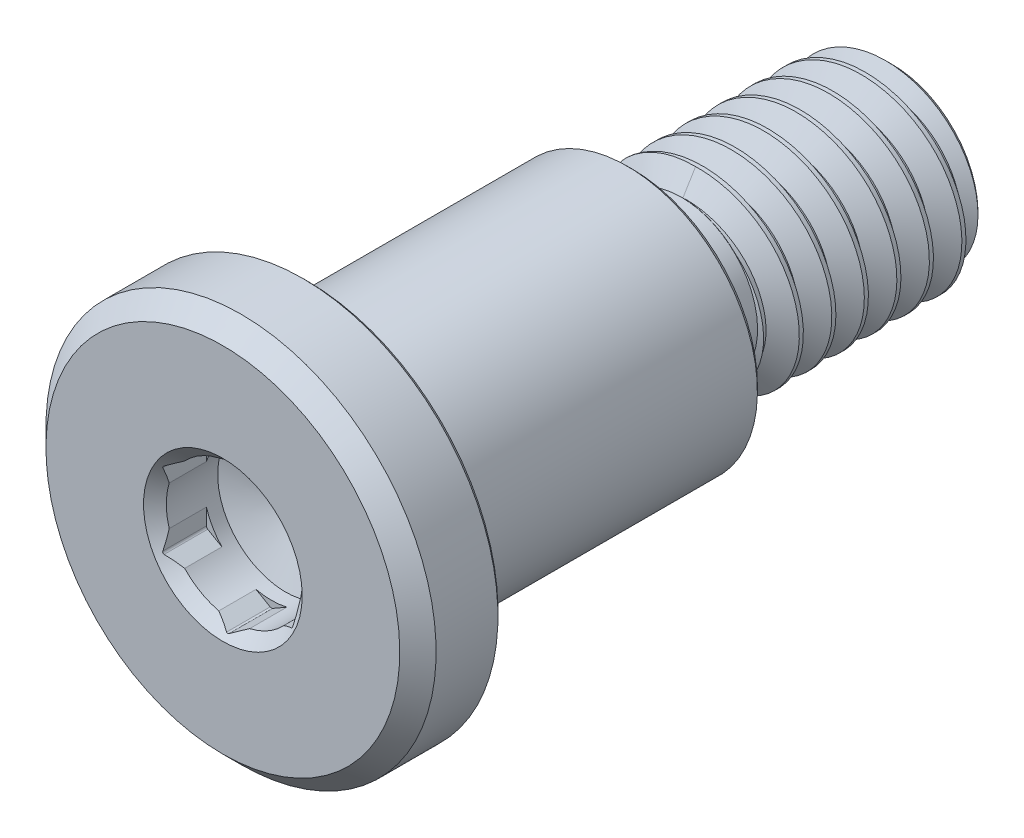
SolidWorks part; units mm, degrees
ref_plane "Front Plane" through (0, 0, 0) normal (0, 0, 1) x (1, 0, 0)
ref_plane "Top Plane" through (0, 0, 0) normal (0, 1, 0) x (1, 0, 0)
ref_plane "Right Plane" through (0, 0, 0) normal (1, 0, 0) x (0, 0, -1)
sketch "Sketch1" plane through (0, 0, 0) normal (1, 0, 0) x (0, 0, -1)
  line L0 (9, 0) -> (0, 0) construction
  line L1 (0, 0) -> (-1.3, 0) construction
  line L2 (-1.3, 3) -> (-1.3, -3) construction
  line L3 (0, 3) -> (0, -3) construction
  line L4 (5, 1.5) -> (9, 1.5) construction
  line L5 (8.9688, 1.5541) -> (9.4688, 1.5541) construction
  line L6 (9.4688, 1.5541) -> (9.2188, 1.1211) construction
  line L7 (9.2188, 1.1211) -> (8.9688, 1.5541) construction
  line L8 (9, 1.5) -> (9.4375, 1.5) construction
  line L9 (9.1875, 1.1752) -> (9.25, 1.1752) construction
  line L10 (9.2188, 1.1211) -> (9.2188, 1.1752) construction
  line L11 (9.2188, 1.5) -> (9.2188, 1.5541) construction
  line L12 (-1.3, 1) -> (-0.335, 1) construction
  line L13 (-0.335, 1) -> (-0.335, -1) construction
  line L14 (-0.335, -1) -> (-1.3, -1) construction
  line L15 (5, 2) -> (5, -2) construction
  line L16 (-1.3, 3) -> (0, 3) construction
  line L17 (5, -1.5) -> (9, -1.5) construction
  point P12 (-0.335, 0)
  point P27 (5, 0)
  point P36 (8.25, -1.5)
  dimension "Screw Size Decimal Equivalent" = 3
  dimension "Thread Length" = 4
  dimension "Shoulder Diameter" = 4
  dimension "Head Height" = 1.3
  dimension "Head Diameter" = 6
  dimension "Drive Size" = 2
  dimension "Thread Pitch" = 0.5
  dimension "Pitch/8" = 0.0625
  dimension "Thread Note" = 0.75
  dimension "Shoulder Length" = 5
  dimension "Approximate Drive Depth" = 0.965
sketch "Sketch2" plane through (0, 0, 0) normal (1, 0, 0) x (0, 0, -1)
  line L0 (-1.3, 3) -> (0, 3)
  line L1 (0, 3) -> (0, 2)
  line L2 (0, 2) -> (5, 2)
  line L3 (5, 2) -> (5, 1.5)
  line L4 (5, 1.5) -> (9, 1.5)
  line L5 (9, 1.5) -> (9, 0)
  line L6 (9, 0) -> (-1.3, 0)
  line L7 (-1.3, 0) -> (-1.3, 3)
revolve "Revolve1" add sketch "Sketch2" angle 360 about L1
chamfer "Chamfer1" distance 0.2795 angle 45 1 edges at (0, 3, 1.3)
chamfer "Chamfer4" distance 0.0699 angle 45 1 edges at (0, 3, 0)
sketch "Sketch3" plane through (0, 0, 0) normal (1, 0, 0) x (0, 0, -1)
  line L0 (0, 2) -> (0.4249, 2)
  line L1 (5, 2) -> (0, 2) construction
  line L2 (0.4249, 2) -> (0.3005, 1.8755)
  line L3 (0, 3) -> (0, -3) construction
  line L4 (0, 1.824) -> (0.176, 1.824) construction
  arc A0 (0.3005, 1.8755) -> (0, 2) centre (0.176, 2) cw
  dimension "D2" = 0.176
  dimension "D1" = 45
revolve "Cut-Revolve1" cut sketch "Sketch3" angle 360 about L0
sketch "Sketch4" plane through (0, 0, 0) normal (1, 0, 0) x (0, 0, -1)
  line L0 (5, 1.5) -> (9, 1.5) construction
  line L1 (5, 1.5) -> (5.939, 1.5)
  line L2 (5, 1.5) -> (5, 1.1727)
  line L3 (5, 1.1727) -> (5.75, 1.1727)
  line L4 (5.939, 1.5) -> (5.75, 1.1727)
  line L5 (5, 2) -> (5, -2) construction
  line L7 (9.1875, 1.1752) -> (9.25, 1.1752) construction
  point P8 (5.7515, 1.1752)
  dimension "D2" = 60
  dimension "D3" = 0.0025
revolve "Cut-Revolve2" cut sketch "Sketch4" angle 360 about L0
chamfer "Chamfer2" distance 0.08 angle 45 1 edges at (0, 2, -5)
fillet "Fillet1" radius 0.064 1 edges at (0, 1.1727, -5)
chamfer "Chamfer3" distance 0.1875 angle 45 1 edges at (0, 1.5, -9)
sketch "Sketch11" plane through (0, 0, 1.3) normal (0, 0, 1) x (1, 0, 0)
  circle A0 centre (0, 0) radius 1.045
  dimension "D1" = 2.09
extrude "Cut-Extrude4" cut sketch "Sketch11" against normal up to vertex (0.965 mm away) up to point (0, 1, 0.335)
sketch "Sketch5" plane through (0, 0, 1.3) normal (0, 0, 1) x (1, 0, 0)
  line L1 (0, 1.1547) -> (-1, 0.5774)
  line L2 (-1, 0.5774) -> (-1, -0.5774)
  line L3 (-1, -0.5774) -> (0, -1.1547)
  line L4 (0, -1.1547) -> (1, -0.5774)
  line L5 (1, -0.5774) -> (1, 0.5774)
  line L6 (1, 0.5774) -> (0, 1.1547)
  circle A0 centre (0, 0) radius 1 construction
  circle A1 centre (0, 0) radius 3 construction
extrude "Cut-Extrude1" cut sketch "Sketch5" against normal blind 0.7469
sketch "Sketch6" plane through (0, 0, 1.3) normal (0, 0, 1) x (1, 0, 0)
  circle A0 centre (0, 0) radius 1.22
  dimension "D1" = 2.44
extrude "Cut-Extrude2" cut sketch "Sketch6" against normal up to vertex (0.965 mm away) draft 45 up to point (0, 1, 0.335)
sketch "Sketch9" plane through (0, 0, 0.335) normal (0, 0, 1) x (1, 0, 0)
  circle A0 centre (0, 0) radius 1.045
  circle A2 centre (0, 0) radius 1.045 construction
extrude "Cut-Extrude3" cut sketch "Sketch9" against normal through all draft 70
fillet "Fillet2" radius 0.04 6 edges at (1, 0.5774, 0.8939) (0, 1.1547, 0.8939) (-1, 0.5774, 0.8939) (0, -1.1547, 0.8939) (1, -0.5774, 0.8939) (-1, -0.5774, 0.8939)
fillet "Fillet3" radius 0.2499 1 edges at (0, 2, -0.4249)
ref_plane "Plane1" through (0, 0, -5.75) normal (0, 0, 1) x (1, 0, 0)
split "Split1" trim tools "Plane1" bodies to split 113 resulting bodies 109 110
sketch "Sketch7" plane through (0, 0, 0) normal (1, 0, 0) x (0, 0, -1)
  line L0 (9.1875, 1.1752) -> (9.25, 1.1752)
  line L1 (9.25, 1.1752) -> (9.4531, 1.5271)
  line L2 (9.4688, 1.5541) -> (9.2188, 1.1211) construction
  line L3 (9.4531, 1.5271) -> (8.9844, 1.5271)
  line L4 (9.2188, 1.1211) -> (8.9688, 1.5541) construction
  line L5 (8.9844, 1.5271) -> (9.1875, 1.1752)
  line L6 (9.2188, 1.5) -> (9.2188, 1.5541) construction
  point P12 (9.2188, 1.5271)
sketch "Sketch8" plane through (0, 0, -9) normal (0, 0, -1) x (-1, 0, 0)
  circle A0 centre (0, 0) radius 1.5
curve "Helix/Spiral1" pitch 0.5 height 3.75 turns 7.5
sweep "Cut-Sweep1" cut profiles "Sketch7" path "Helix/Spiral1" align with end faces yes
ref_plane "Plane2" through (0, 0, -5.7515) normal (0, 0, 1) x (1, 0, 0)
sketch "Sketch10" plane through (0, 0, -5.7515) normal (0, 0, 1) x (1, 0, 0)
  circle A0 centre (0, 0) radius 1.1752
extrude "Boss-Extrude1" add sketch "Sketch10" along normal through all draft 60
equation "\"Pitch/8@Sketch1\" = \"Thread Pitch@Sketch1\" / 8"
equation "\"Thread Note@Sketch1\"=\"Thread Pitch@Sketch1\"*1.5"
equation "\"D1@Chamfer1\"=\"Head Height@Sketch1\"*.215"
equation "\"D1@Sketch4\"=\"Thread Pitch@Sketch1\"*1.5"
equation "\"D1@Chamfer2\"=\"Shoulder Diameter@Sketch1\"*.02"
equation "\"D1@Fillet1\" = \"D1@Chamfer2\" * .8"
equation "\"D1@Chamfer3\"=\"Thread Pitch@Sketch1\" * .375"
equation "\"D1@Sketch6\"=\"Drive Size@Sketch1\" * 1.22"
equation "\"D1@Fillet2\"=\"Drive Size@Sketch1\"*.02"
equation "\"D4@Helix/Spiral1\"=\"Thread Pitch@Sketch1\""
equation "\"D3@Helix/Spiral1\"=\"Thread Length@Sketch1\" - \"Thread Pitch@Sketch1\"*.5"
equation "\"Approximate Drive Depth@Sketch1\"=\"Drive Size@Sketch1\"*.4825"
equation "\"D1@Chamfer4\"=\"D1@Chamfer1\"*.25"
equation "\"D2@Sketch3\"=\"Shoulder Diameter@Sketch1\"*.044"
equation "\"D1@Fillet3\"=\"D2@Sketch3\" * 1.42"
equation "\"D1@Sketch11\"=\"Drive Size@Sketch1\"*1.045"
equation "\"D1@Cut-Extrude1\"=\"Approximate Drive Depth@sketch1\"*.774"
